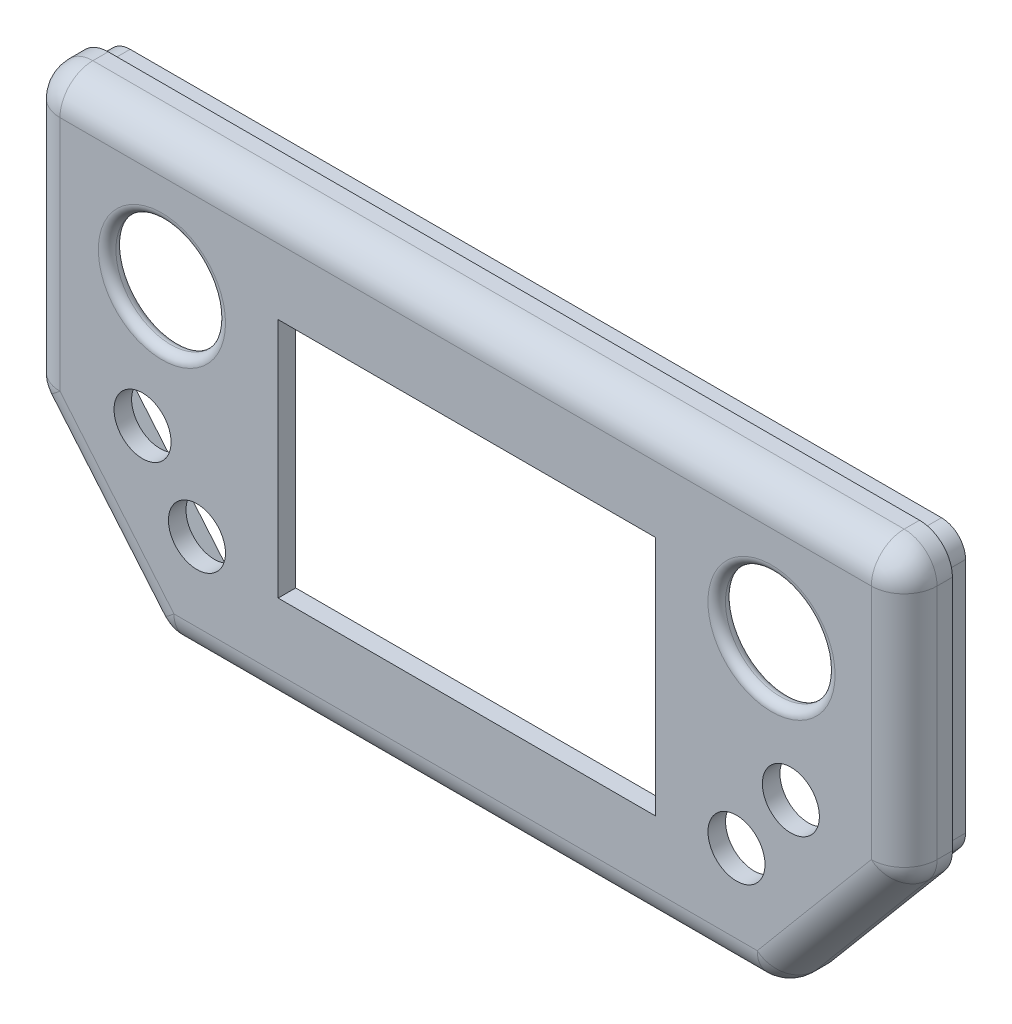
SolidWorks part; units mm, degrees
ref_plane "Front Plane" through (0, 0, 0) normal (0, 0, 1) x (1, 0, 0)
ref_plane "Top Plane" through (0, 0, 0) normal (0, 1, 0) x (1, 0, 0)
ref_plane "Right Plane" through (0, 0, 0) normal (1, 0, 0) x (0, 0, -1)
sketch "Sketch1" plane through (0, 0, 0) normal (0, 0, 1) x (1, 0, 0)
  line L48 (-32.7612, -78.3628) -> (-6.7639, -109.3452)
  line L49 (-34.5159, -19.5243) -> (-34.5159, -73.5419)
  line L50 (157.9841, -12.0243) -> (-27.0159, -12.0243)
  line L51 (165.4841, -73.5419) -> (165.4841, -19.5243)
  line L58 (137.7322, -109.3452) -> (163.7295, -78.3628)
  line L59 (-1.0185, -112.0243) -> (131.9868, -112.0243)
  line L66 (-32.7612, -78.3628) -> (-6.7639, -109.3452)
  line L67 (-34.5159, -19.5243) -> (-34.5159, -73.5419)
  line L68 (157.9841, -12.0243) -> (-27.0159, -12.0243)
  line L69 (165.4841, -73.5419) -> (165.4841, -19.5243)
  line L76 (137.7322, -109.3452) -> (163.7295, -78.3628)
  line L77 (-1.0185, -112.0243) -> (131.9868, -112.0243)
  arc A48 (-6.7639, -109.3452) -> (-1.0185, -112.0243) centre (-1.0185, -104.5243) ccw
  arc A49 (-34.5159, -73.5419) -> (-32.7612, -78.3628) centre (-27.0159, -73.5419) ccw
  arc A50 (-27.0159, -12.0243) -> (-34.5159, -19.5243) centre (-27.0159, -19.5243) ccw
  arc A51 (165.4841, -19.5243) -> (157.9841, -12.0243) centre (157.9841, -19.5243) ccw
  arc A52 (163.7295, -78.3628) -> (165.4841, -73.5419) centre (157.9841, -73.5419) ccw
  arc A53 (131.9868, -112.0243) -> (137.7322, -109.3452) centre (131.9868, -104.5243) ccw
  arc A60 (-6.7639, -109.3452) -> (-1.0185, -112.0243) centre (-1.0185, -104.5243) ccw
  arc A61 (-34.5159, -73.5419) -> (-32.7612, -78.3628) centre (-27.0159, -73.5419) ccw
  arc A68 (-27.0159, -12.0243) -> (-34.5159, -19.5243) centre (-27.0159, -19.5243) ccw
  arc A69 (165.4841, -19.5243) -> (157.9841, -12.0243) centre (157.9841, -19.5243) ccw
  arc A70 (163.7295, -78.3628) -> (165.4841, -73.5419) centre (157.9841, -73.5419) ccw
  arc A71 (131.9868, -112.0243) -> (137.7322, -109.3452) centre (131.9868, -104.5243) ccw
  dimension "D1" = 0
extrude "Boss-Extrude1" add sketch "Sketch1" along normal blind 11
shell "Shell1" thickness 4 removed face at (65.4841, -67.3435, 0)
fillet "Fillet1" radius 7.5 12 edges at (65.4841, -112.0243, 11) (-19.7625, -93.854, 11) (-34.0636, -76.1071, 11) (-34.5159, -46.5331, 11) (-32.3192, -14.221, 11) (65.4841, -12.0243, 11) (163.2874, -14.221, 11) (165.4841, -46.5331, 11) (165.0318, -76.1071, 11) (150.7308, -93.854, 11) (135.1565, -111.3216, 11) (-4.1882, -111.3216, 11)
sketch "Sketch2" plane through (0, 0, 0) normal (0, 0, -1) x (-1, 0, 0)
  line L6 (5.2318, -108.0597) -> (31.2291, -77.0773)
  line L15 (5.2318, -108.0597) -> (31.2291, -77.0773)
  line L25 (32.5159, -73.5419) -> (32.5159, -19.5243)
  line L26 (-131.9868, -110.0243) -> (1.0185, -110.0243)
  line L32 (-131.9868, -110.0243) -> (1.0185, -110.0243)
  line L35 (32.5159, -73.5419) -> (32.5159, -19.5243)
  line L37 (27.0159, -14.0243) -> (-157.9841, -14.0243)
  line L39 (3.6997, -106.7741) -> (29.697, -75.7917)
  line L41 (3.6997, -106.7741) -> (29.697, -75.7917)
  line L47 (-131.9868, -108.0243) -> (1.0185, -108.0243)
  line L53 (-131.9868, -108.0243) -> (1.0185, -108.0243)
  line L54 (30.5159, -73.5419) -> (30.5159, -19.5243)
  line L60 (27.0159, -14.0243) -> (-157.9841, -14.0243)
  line L61 (-163.4841, -19.5243) -> (-163.4841, -73.5419)
  line L62 (-163.4841, -19.5243) -> (-163.4841, -73.5419)
  line L63 (-162.1974, -77.0773) -> (-136.2001, -108.0597)
  line L64 (-162.1974, -77.0773) -> (-136.2001, -108.0597)
  line L65 (30.5159, -73.5419) -> (30.5159, -19.5243)
  line L66 (27.0159, -16.0243) -> (-157.9841, -16.0243)
  line L67 (27.0159, -16.0243) -> (-157.9841, -16.0243)
  line L68 (-161.4841, -19.5243) -> (-161.4841, -73.5419)
  line L69 (-161.4841, -19.5243) -> (-161.4841, -73.5419)
  line L70 (-160.6653, -75.7917) -> (-134.668, -106.7741)
  line L71 (-160.6653, -75.7917) -> (-134.668, -106.7741)
  arc A12 (1.0185, -110.0243) -> (5.2318, -108.0597) centre (1.0185, -104.5243) ccw
  arc A16 (1.0185, -110.0243) -> (5.2318, -108.0597) centre (1.0185, -104.5243) ccw
  arc A25 (31.2291, -77.0773) -> (32.5159, -73.5419) centre (27.0159, -73.5419) ccw
  arc A34 (31.2291, -77.0773) -> (32.5159, -73.5419) centre (27.0159, -73.5419) ccw
  arc A43 (32.5159, -19.5243) -> (27.0159, -14.0243) centre (27.0159, -19.5243) ccw
  arc A45 (32.5159, -19.5243) -> (27.0159, -14.0243) centre (27.0159, -19.5243) ccw
  arc A47 (1.0185, -108.0243) -> (3.6997, -106.7741) centre (1.0185, -104.5243) ccw
  arc A61 (1.0185, -108.0243) -> (3.6997, -106.7741) centre (1.0185, -104.5243) ccw
  arc A63 (29.697, -75.7917) -> (30.5159, -73.5419) centre (27.0159, -73.5419) ccw
  arc A65 (29.697, -75.7917) -> (30.5159, -73.5419) centre (27.0159, -73.5419) ccw
  arc A67 (30.5159, -19.5243) -> (27.0159, -16.0243) centre (27.0159, -19.5243) ccw
  arc A69 (30.5159, -19.5243) -> (27.0159, -16.0243) centre (27.0159, -19.5243) ccw
  arc A71 (-157.9841, -14.0243) -> (-163.4841, -19.5243) centre (-157.9841, -19.5243) ccw
  arc A72 (-157.9841, -14.0243) -> (-163.4841, -19.5243) centre (-157.9841, -19.5243) ccw
  arc A73 (-163.4841, -73.5419) -> (-162.1974, -77.0773) centre (-157.9841, -73.5419) ccw
  arc A74 (-163.4841, -73.5419) -> (-162.1974, -77.0773) centre (-157.9841, -73.5419) ccw
  arc A75 (-136.2001, -108.0597) -> (-131.9868, -110.0243) centre (-131.9868, -104.5243) ccw
  arc A76 (-136.2001, -108.0597) -> (-131.9868, -110.0243) centre (-131.9868, -104.5243) ccw
  arc A77 (-157.9841, -16.0243) -> (-161.4841, -19.5243) centre (-157.9841, -19.5243) ccw
  arc A78 (-157.9841, -16.0243) -> (-161.4841, -19.5243) centre (-157.9841, -19.5243) ccw
  arc A79 (-161.4841, -73.5419) -> (-160.6653, -75.7917) centre (-157.9841, -73.5419) ccw
  arc A80 (-161.4841, -73.5419) -> (-160.6653, -75.7917) centre (-157.9841, -73.5419) ccw
  arc A81 (-134.668, -106.7741) -> (-131.9868, -108.0243) centre (-131.9868, -104.5243) ccw
  arc A82 (-134.668, -106.7741) -> (-131.9868, -108.0243) centre (-131.9868, -104.5243) ccw
  dimension "D1" = 2
  dimension "D2" = 4
extrude "Boss-Extrude2" add sketch "Sketch2" along normal blind 5
sketch "Sketch3" plane through (0, 0, 11) normal (0, 0, 1) x (1, 0, 0)
  line L1 (22.7341, -34.5243) -> (108.7341, -34.5243)
  line L2 (22.7341, -34.5243) -> (22.7341, -89.5243)
  line L3 (22.7341, -89.5243) -> (108.7341, -89.5243)
  line L4 (108.7341, -34.5243) -> (108.7341, -89.5243)
  line L5 (-1.0185, -104.5243) -> (131.9868, -104.5243) construction
  dimension "D1" = 86
  dimension "D2" = 55
  dimension "D3" = 15
extrude "Cut-Extrude1" cut sketch "Sketch3" against normal blind 10
sketch "Sketch4" plane through (0, 0, 11) normal (0, 0, 1) x (1, 0, 0)
  line L0 (65.7341, -15.7243) -> (65.7341, -105.7243) construction
  line L1 (-27.0159, -73.5419) -> (-1.0185, -104.5243) construction
  circle A0 centre (-3.7659, -41.2243) radius 12.5
  circle A2 centre (-8.1836, -70.9616) radius 6.5
  circle A3 centre (4.2185, -86.6519) radius 6.5
  circle A4 centre (127.2497, -86.6519) radius 6.5
  circle A5 centre (139.6519, -70.9616) radius 6.5
  circle A6 centre (135.2341, -41.2243) radius 12.5
  dimension "D1" = 25
  dimension "D2" = 13
  dimension "D7" = 20
  dimension "D3" = 15.5
extrude "Cut-Extrude2" cut sketch "Sketch4" against normal blind 10
fillet "Fillet2" radius 2 4 edges at (8.7341, -41.2243, 7) (8.7341, -41.2243, 11) (147.7341, -41.2243, 7) (122.7341, -41.2243, 11)
